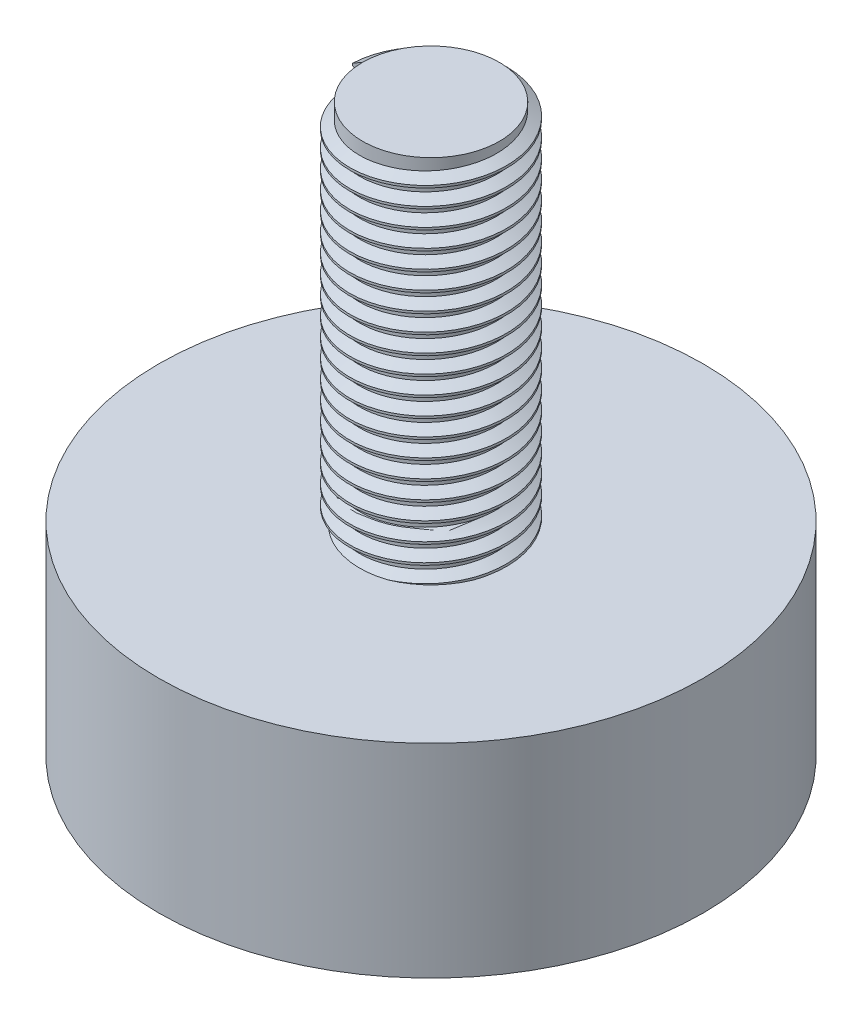
SolidWorks part; units mm, degrees
material "1.4000 (X6Cr13)"
ref_plane "Plan de face" through (0, 0, 0) normal (0, 0, 1) x (1, 0, 0)
ref_plane "Plan de dessus" through (0, 0, 0) normal (0, 1, 0) x (1, 0, 0)
ref_plane "Plan de droite" through (0, 0, 0) normal (1, 0, 0) x (0, 0, -1)
sketch "Esquisse1" plane through (0, 0, 0) normal (0, 0, 1) x (1, 0, 0)
  line L0 (3.8774, -0.0325) -> (7.5, 0)
  line L1 (0, 0) -> (30, 0) construction
  line L2 (0, 0) -> (0, 30) construction
  line L3 (0, 30) -> (30, 30) construction
  line L4 (30, 0) -> (30, 30) construction
  line L5 (7.5, 0) -> (7.5, 5.6)
  line L6 (7.5, 5.6) -> (0, 5.6)
  line L7 (0, 5.6) -> (0, 5.4)
  arc A0 (3.8774, -0.0325) -> (0, 5.4) centre (0, 1.3) ccw
  dimension "D6" = 8.2
  dimension "D1" = 30
  dimension "D2" = 30
  dimension "D3" = 5.6
  dimension "D4" = 7.5
  dimension "D5" = 1.3
revolve "Révolution1" add sketch "Esquisse1" angle 360 about L2
sketch "Esquisse2" plane through (0, 5.6, 0) normal (0, 1, 0) x (1, 0, 0)
  circle A0 centre (0, 0) radius 1.8847
  dimension "D1" = 3.7695
extrude "Boss.-Extru.1" add sketch "Esquisse2" along normal blind 10
thread "Filetage1" pitch 0.5 method extrude profile "Profil de filetage1" start angle 0, offset 0, length 10, pitch 0.5, diameter 3.7695
ref_plane "Plan1" through (-1.8847, 15.6, 0) normal (0, 0, 1) x (-1, 0, 0)
sketch "Profil de filetage1" plane through (-1.8847, 15.6, 0) normal (0, 0, 1) x (-1, 0, 0)
  line L0 (0, 0) -> (0, 0.5) construction
  line L1 (0, 0) -> (0.2706, 0.1562)
  line L2 (0.2706, 0.1562) -> (0.2706, 0.2187)
  line L3 (0.2706, 0.2187) -> (0, 0.375)
  line L4 (0.2706, 0.1875) -> (0, 0.1875) construction
  line L11 (0, 0) -> (0, 0.375)
  point P2 (0, 0)
  dimension "Pitch" = 0.5
  dimension "Profile_Angle" = 60
  dimension "Profile_Land" = 0.0625
  dimension "Profile_Height" = 0.2706
